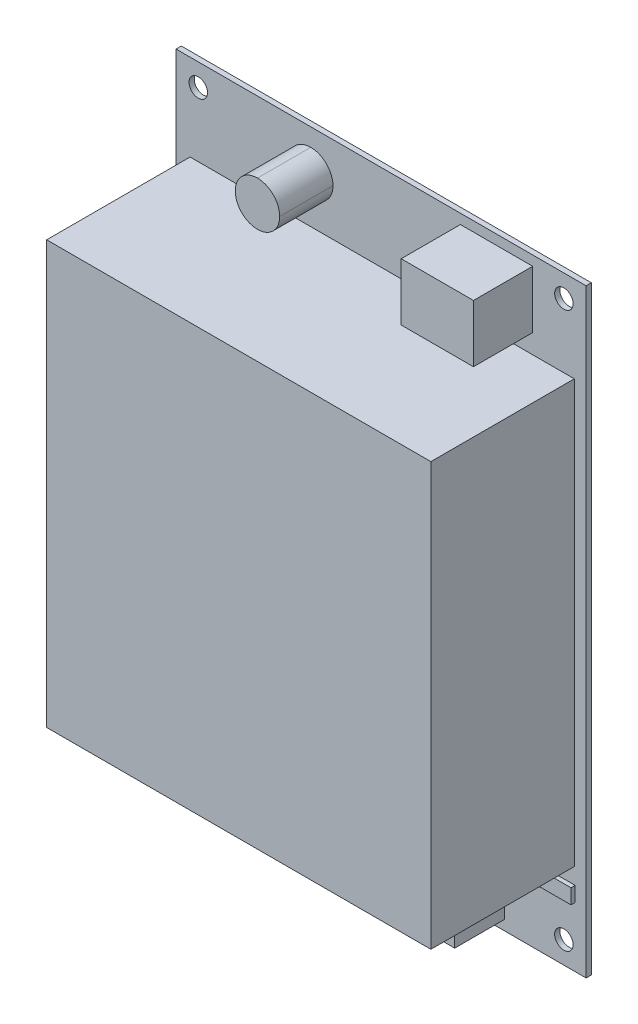
SolidWorks part; units mm, degrees
ref_plane "Front Plane" through (0, 0, 0) normal (0, 0, 1) x (1, 0, 0)
ref_plane "Top Plane" through (0, 0, 0) normal (0, 1, 0) x (1, 0, 0)
ref_plane "Right Plane" through (0, 0, 0) normal (1, 0, 0) x (0, 0, -1)
sketch "Sketch1" plane through (0, 0, 0) normal (0, 0, 1) x (1, 0, 0)
  line L0 (0, 102.87) -> (0, 0)
  line L1 (0, 0) -> (70.358, 0)
  line L2 (70.358, 0) -> (70.358, 102.87)
  line L3 (70.358, 102.87) -> (0, 102.87)
extrude "BOARD" add sketch "Sketch1" along normal blind 0.8992 separate body
ref_plane "Plane1" through (0, 0, 0.8992) normal (0, 0, 1) x (1, 0, 0)
sketch "Sketch48" plane through (0, 0, 0) normal (0, 0, 1) x (1, 0, 0)
  line L0 (20.447, 51.036) -> (22.987, 51.036)
  line L1 (22.987, 51.036) -> (22.987, 50.0659)
  line L2 (22.987, 50.0659) -> (20.447, 50.0659)
  line L3 (20.447, 50.0659) -> (20.447, 51.036)
extrude "0603-R-35" add sketch "Sketch48" against normal blind 0.508 separate body
sketch "Sketch49" plane through (0, 0, 0) normal (0, 0, 1) x (1, 0, 0)
  line L0 (20.447, 49.6331) -> (22.987, 49.6331)
  line L1 (22.987, 49.6331) -> (22.987, 48.6631)
  line L2 (22.987, 48.6631) -> (20.447, 48.6631)
  line L3 (20.447, 48.6631) -> (20.447, 49.6331)
extrude "0603-R-36" add sketch "Sketch49" against normal blind 0.508 separate body
sketch "Sketch50" plane through (0, 0, 0) normal (0, 0, 1) x (1, 0, 0)
  line L0 (20.447, 48.227) -> (22.987, 48.227)
  line L1 (22.987, 48.227) -> (22.987, 47.257)
  line L2 (22.987, 47.257) -> (20.447, 47.257)
  line L3 (20.447, 47.257) -> (20.447, 48.227)
extrude "0603-R-37" add sketch "Sketch50" against normal blind 0.508 separate body
sketch "Sketch59" plane through (0, 0, 0) normal (0, 0, 1) x (1, 0, 0)
  line L0 (22.987, 52.85) -> (20.447, 52.85)
  line L1 (20.447, 52.85) -> (20.447, 53.8201)
  line L2 (20.447, 53.8201) -> (22.987, 53.8201)
  line L3 (22.987, 53.8201) -> (22.987, 52.85)
extrude "0603-RB-1" add sketch "Sketch59" against normal blind 0.254 separate body
sketch "Sketch60" plane through (0, 0, 0) normal (0, 0, 1) x (1, 0, 0)
  line L0 (19.177, 50.056) -> (16.637, 50.056)
  line L1 (16.637, 50.056) -> (16.637, 51.0261)
  line L2 (16.637, 51.0261) -> (19.177, 51.0261)
  line L3 (19.177, 51.0261) -> (19.177, 50.056)
extrude "0603-R-44" add sketch "Sketch60" against normal blind 0.508 separate body
sketch "Sketch61" plane through (0, 0, 0) normal (0, 0, 1) x (1, 0, 0)
  line L0 (19.177, 47.262) -> (16.637, 47.262)
  line L1 (16.637, 47.262) -> (16.637, 48.2321)
  line L2 (16.637, 48.2321) -> (19.177, 48.2321)
  line L3 (19.177, 48.2321) -> (19.177, 47.262)
extrude "0603-RA-1" add sketch "Sketch61" against normal blind 0.254 separate body
sketch "Sketch62" plane through (0, 0, 0) normal (0, 0, 1) x (1, 0, 0)
  line L0 (16.637, 55.227) -> (19.177, 55.227)
  line L1 (19.177, 55.227) -> (19.177, 54.2569)
  line L2 (19.177, 54.2569) -> (16.637, 54.2569)
  line L3 (16.637, 54.2569) -> (16.637, 55.227)
extrude "0603-R-45" add sketch "Sketch62" against normal blind 0.508 separate body
sketch "Sketch63" plane through (0, 0, 0) normal (0, 0, 1) x (1, 0, 0)
  line L0 (16.637, 53.83) -> (19.177, 53.83)
  line L1 (19.177, 53.83) -> (19.177, 52.8599)
  line L2 (19.177, 52.8599) -> (16.637, 52.8599)
  line L3 (16.637, 52.8599) -> (16.637, 53.83)
extrude "0603-R-46" add sketch "Sketch63" against normal blind 0.508 separate body
sketch "Sketch64" plane through (0, 0, 0) normal (0, 0, 1) x (1, 0, 0)
  line L0 (19.177, 55.644) -> (16.637, 55.644)
  line L1 (16.637, 55.644) -> (16.637, 56.6141)
  line L2 (16.637, 56.6141) -> (19.177, 56.6141)
  line L3 (19.177, 56.6141) -> (19.177, 55.644)
extrude "0603-R-47" add sketch "Sketch64" against normal blind 0.508 separate body
sketch "Sketch65" plane through (0, 0, 0) normal (0, 0, 1) x (1, 0, 0)
  line L0 (19.177, 51.453) -> (16.637, 51.453)
  line L1 (16.637, 51.453) -> (16.637, 52.4231)
  line L2 (16.637, 52.4231) -> (19.177, 52.4231)
  line L3 (19.177, 52.4231) -> (19.177, 51.453)
extrude "0603-R-48" add sketch "Sketch65" against normal blind 0.508 separate body
sketch "Sketch66" plane through (0, 0, 0) normal (0, 0, 1) x (1, 0, 0)
  line L0 (23.0154, 51.466) -> (20.4754, 51.466)
  line L1 (20.4754, 51.466) -> (20.4754, 52.436)
  line L2 (20.4754, 52.436) -> (23.0154, 52.436)
  line L3 (23.0154, 52.436) -> (23.0154, 51.466)
extrude "0603-R-49" add sketch "Sketch66" against normal blind 0.508 separate body
sketch "Sketch67" plane through (0, 0, 0) normal (0, 0, 1) x (1, 0, 0)
  line L0 (16.637, 49.639) -> (19.177, 49.639)
  line L1 (19.177, 49.639) -> (19.177, 48.6689)
  line L2 (19.177, 48.6689) -> (16.637, 48.6689)
  line L3 (16.637, 48.6689) -> (16.637, 49.639)
extrude "0603-R-50" add sketch "Sketch67" against normal blind 0.508 separate body
sketch "Sketch74" plane through (0, 0, 0) normal (0, 0, 1) x (1, 0, 0)
  line L0 (22.987, 55.644) -> (20.447, 55.644)
  line L1 (20.447, 55.644) -> (20.447, 56.6141)
  line L2 (20.447, 56.6141) -> (22.987, 56.6141)
  line L3 (22.987, 56.6141) -> (22.987, 55.644)
extrude "0603-R-56" add sketch "Sketch74" against normal blind 0.508 separate body
sketch "Sketch75" plane through (0, 0, 0) normal (0, 0, 1) x (1, 0, 0)
  line L0 (22.987, 54.247) -> (20.447, 54.247)
  line L1 (20.447, 54.247) -> (20.447, 55.2171)
  line L2 (20.447, 55.2171) -> (22.987, 55.2171)
  line L3 (22.987, 55.2171) -> (22.987, 54.247)
extrude "0603-RB-2" add sketch "Sketch75" against normal blind 0.254 separate body
sketch "Sketch78" plane through (0, 0, 0.8992) normal (0, 0, 1) x (1, 0, 0)
  line L0 (16.637, 10.668) -> (9.017, 10.668)
  line L1 (9.017, 10.668) -> (9.017, 3.048)
  line L2 (9.017, 3.048) -> (16.637, 3.048)
  line L3 (16.637, 3.048) -> (16.637, 10.668)
extrude "SMA-50-TH-1" add sketch "Sketch78" along normal blind 9.144 separate body
sketch "Sketch79" plane through (0, 0, 0.8992) normal (0, 0, 1) x (1, 0, 0)
  line L0 (26.924, 99.822) -> (19.304, 99.822)
  line L1 (19.304, 99.822) -> (19.304, 92.202)
  line L2 (19.304, 92.202) -> (26.924, 92.202)
  line L3 (26.924, 92.202) -> (26.924, 99.822)
extrude "SMA-50-TH-2" add sketch "Sketch79" along normal blind 9.144 separate body
sketch "Sketch83" plane through (0, 0, 0.8992) normal (0, 0, 1) x (1, 0, 0)
  line L0 (54.356, 10.287) -> (60.104, 10.287)
  line L1 (60.104, 10.287) -> (60.104, 12.827)
  line L2 (60.104, 12.827) -> (54.356, 12.827)
  line L3 (54.356, 12.827) -> (54.356, 10.287)
extrude "0805_POL-1" add sketch "Sketch83" along normal blind 0.7112 separate body
sketch "Sketch84" plane through (0, 0, 0.8992) normal (0, 0, 1) x (1, 0, 0)
  line L0 (62.738, 10.287) -> (68.486, 10.287)
  line L1 (68.486, 10.287) -> (68.486, 12.827)
  line L2 (68.486, 12.827) -> (62.738, 12.827)
  line L3 (62.738, 12.827) -> (62.738, 10.287)
extrude "0805_POL-2" add sketch "Sketch84" along normal blind 0.7112 separate body
sketch "Sketch85" plane through (0, 0, 0.8992) normal (0, 0, 1) x (1, 0, 0)
  line L0 (61.359, 12.827) -> (61.359, 10.287)
  line L1 (61.359, 10.287) -> (62.3291, 10.287)
  line L2 (62.3291, 10.287) -> (62.3291, 12.827)
  line L3 (62.3291, 12.827) -> (61.359, 12.827)
extrude "0603-R-58" add sketch "Sketch85" along normal blind 0.508 separate body
sketch "Sketch86" plane through (0, 0, 0.8992) normal (0, 0, 1) x (1, 0, 0)
  line L0 (52.977, 12.827) -> (52.977, 10.287)
  line L1 (52.977, 10.287) -> (53.9471, 10.287)
  line L2 (53.9471, 10.287) -> (53.9471, 12.827)
  line L3 (53.9471, 12.827) -> (52.977, 12.827)
extrude "0603-R-59" add sketch "Sketch86" along normal blind 0.508 separate body
sketch "Sketch110" plane through (0, 0, 0.8992) normal (0, 0, 1) x (1, 0, 0)
  line L0 (25.654, 3.048) -> (33.274, 3.048)
  line L1 (33.274, 3.048) -> (33.274, 10.668)
  line L2 (33.274, 10.668) -> (25.654, 10.668)
  line L3 (25.654, 10.668) -> (25.654, 3.048)
extrude "SMA-50-TH-3" add sketch "Sketch110" along normal blind 9.144 separate body
sketch "Sketch117" plane through (0, 0, 0.8992) normal (0, 0, 1) x (1, 0, 0)
  line L0 (36.9931, 1.668) -> (47.4929, 1.668)
  line L1 (47.4929, 1.668) -> (47.4929, 7.8966)
  line L2 (47.4929, 7.8966) -> (36.9931, 7.8966)
  line L3 (36.9931, 7.8966) -> (36.9931, 1.668)
extrude "HDR_SHERLOCK_4P_V-1" add sketch "Sketch117" along normal blind 8.509 separate body
sketch "Sketch118" plane through (0, 0, 0.8992) normal (0, 0, 1) x (1, 0, 0)
  line L0 (61.1909, 101.1829) -> (48.7911, 101.1829)
  line L1 (48.7911, 101.1829) -> (48.7911, 91.329)
  line L2 (48.7911, 91.329) -> (61.1909, 91.329)
  line L3 (61.1909, 91.329) -> (61.1909, 101.1829)
extrude "HDR_MFITJR_2R2P-V-1" add sketch "Sketch118" along normal blind 10.16 separate body
sketch "Sketch119" plane through (0, 0, 0.8992) normal (0, 0, 1) x (1, 0, 0)
  line L0 (49.8201, 1.668) -> (56.3199, 1.668)
  line L1 (56.3199, 1.668) -> (56.3199, 7.972)
  line L2 (56.3199, 7.972) -> (49.8201, 7.972)
  line L3 (49.8201, 7.972) -> (49.8201, 1.668)
extrude "HDR_SHERLOCK_2P_V-1" add sketch "Sketch119" along normal blind 8.509 separate body
sketch "Sketch121" plane through (0, 0, 0) normal (0, 0, 1) x (1, 0, 0)
  line L0 (32.4599, 29.975) -> (38.814, 29.975)
  line L1 (38.814, 29.975) -> (38.814, 26.8209)
  line L2 (38.814, 26.8209) -> (32.4599, 26.8209)
  line L3 (32.4599, 26.8209) -> (32.4599, 29.975)
extrude "TSSOP8-1" add sketch "Sketch121" against normal blind 0.9906 separate body
sketch "Sketch122" plane through (0, 0, 0) normal (0, 0, 1) x (1, 0, 0)
  line L0 (37.1602, 21.6027) -> (37.1602, 26.5557)
  line L1 (37.1602, 26.5557) -> (38.9382, 26.5557)
  line L2 (38.9382, 26.5557) -> (38.9382, 21.6027)
  line L3 (38.9382, 21.6027) -> (37.1602, 21.6027)
extrude "1206-R-5" add sketch "Sketch122" against normal blind 0.508 separate body
sketch "Sketch124" plane through (0, 0, 0.8992) normal (0, 0, 1) x (1, 0, 0)
  line L0 (37.592, 10.287) -> (43.34, 10.287)
  line L1 (43.34, 10.287) -> (43.34, 12.827)
  line L2 (43.34, 12.827) -> (37.592, 12.827)
  line L3 (37.592, 12.827) -> (37.592, 10.287)
extrude "0805_POL-3" add sketch "Sketch124" along normal blind 0.7112 separate body
sketch "Sketch125" plane through (0, 0, 0.8992) normal (0, 0, 1) x (1, 0, 0)
  line L0 (45.974, 10.287) -> (51.722, 10.287)
  line L1 (51.722, 10.287) -> (51.722, 12.827)
  line L2 (51.722, 12.827) -> (45.974, 12.827)
  line L3 (45.974, 12.827) -> (45.974, 10.287)
extrude "0805_POL-4" add sketch "Sketch125" along normal blind 0.7112 separate body
sketch "Sketch126" plane through (0, 0, 0) normal (0, 0, 1) x (1, 0, 0)
  line L0 (35.6108, 25.3672) -> (33.0708, 25.3672)
  line L1 (33.0708, 25.3672) -> (33.0708, 26.3373)
  line L2 (33.0708, 26.3373) -> (35.6108, 26.3373)
  line L3 (35.6108, 26.3373) -> (35.6108, 25.3672)
extrude "0603-R-67" add sketch "Sketch126" against normal blind 0.508 separate body
sketch "Sketch127" plane through (0, 0, 0) normal (0, 0, 1) x (1, 0, 0)
  line L0 (39.878, 28.7348) -> (42.418, 28.7348)
  line L1 (42.418, 28.7348) -> (42.418, 27.7647)
  line L2 (42.418, 27.7647) -> (39.878, 27.7647)
  line L3 (39.878, 27.7647) -> (39.878, 28.7348)
extrude "0603-R-68" add sketch "Sketch127" against normal blind 0.508 separate body
sketch "Sketch128" plane through (0, 0, 0.8992) normal (0, 0, 1) x (1, 0, 0)
  line L0 (44.595, 12.827) -> (44.595, 10.287)
  line L1 (44.595, 10.287) -> (45.5651, 10.287)
  line L2 (45.5651, 10.287) -> (45.5651, 12.827)
  line L3 (45.5651, 12.827) -> (44.595, 12.827)
extrude "0603-R-69" add sketch "Sketch128" along normal blind 0.508 separate body
sketch "Sketch129" plane through (0, 0, 0.8992) normal (0, 0, 1) x (1, 0, 0)
  line L0 (37.193, 10.287) -> (37.193, 12.827)
  line L1 (37.193, 12.827) -> (36.2229, 12.827)
  line L2 (36.2229, 12.827) -> (36.2229, 10.287)
  line L3 (36.2229, 10.287) -> (37.193, 10.287)
extrude "0603-R-70" add sketch "Sketch129" along normal blind 0.508 separate body
sketch "Sketch130" plane through (0, 0, 0.8992) normal (0, 0, 1) x (1, 0, 0)
  line L0 (36.861, 84.2373) -> (36.861, 57.4373)
  line L1 (36.861, 57.4373) -> (46.197, 57.4373)
  line L2 (46.197, 57.4373) -> (46.197, 84.2373)
  line L3 (46.197, 84.2373) -> (36.861, 84.2373)
extrude "CAP_AXL_18MM_8MM-1" add sketch "Sketch130" along normal blind 12.4968 separate body
hole_wizard "1/8 (0.125) Diameter Hole1" positions "3DSketch1" profile "Sketch138" hole size "1/8" standard "Ansi Inch"
sketch3d "3DSketch1"
  point P0 (3.81, 99.06, 0.8992)
  point P2 (66.548, 99.06, 0.8992)
  point P4 (3.6372, 3.9715, 0.8992)
  point P6 (66.548, 3.81, 0.8992)
sketch "Sketch138" plane through (3.81, 99.06, 0.8992) normal (1, 0, 0) x (0, -1, 0)
  line L0 (0, 0) -> (0, 26.3539)
  line L1 (0, 26.3539) -> (1.5875, 25.4)
  line L2 (1.5875, 25.4) -> (1.5875, 0)
  line L5 (1.5875, 0) -> (0, 0)
  line L10 (0, 26.3539) -> (-1.5875, 25.4) construction
  line L11 (0, -6.35) -> (0, 107.95) construction
  dimension "Hole Dia." = 3.175
  dimension "Hole Depth" = 25.4
  dimension "Drill Angle" = 118
sketch "Sketch139" plane through (0, 0, 0.8992) normal (0, 0, 1) x (1, 0, 0)
  line L1 (2.4054, 88.0286) -> (68.3332, 88.0286)
  line L2 (2.4054, 88.0286) -> (2.4054, 15.5541)
  line L3 (2.4054, 15.5541) -> (68.3332, 15.5541)
  line L4 (68.3332, 88.0286) -> (68.3332, 15.5541)
extrude "Extrude126" add sketch "Sketch139" along normal blind 24.6091
fillet "Fillet3" radius 3.81 1 edges at (26.924, 92.202, 5.4712)
fillet "Fillet4" radius 3.81 1 edges at (26.924, 99.822, 5.4712)
fillet "Fillet5" radius 3.81 1 edges at (19.304, 99.822, 5.4712)
fillet "Fillet6" radius 3.81 1 edges at (19.304, 92.202, 5.4712)
fillet "Fillet7" radius 3.81 1 edges at (33.274, 10.668, 5.4712)
fillet "Fillet8" radius 3.81 1 edges at (33.274, 3.048, 5.4712)
fillet "Fillet9" radius 3.81 1 edges at (25.654, 3.048, 5.4712)
fillet "Fillet10" radius 3.81 1 edges at (25.654, 10.668, 5.4712)
fillet "Fillet11" radius 3.81 1 edges at (9.017, 3.048, 5.4712)
fillet "Fillet12" radius 3.81 1 edges at (9.017, 10.668, 5.4712)
fillet "Fillet13" radius 3.81 1 edges at (16.637, 3.048, 5.4712)
fillet "Fillet14" radius 3.81 1 edges at (16.637, 10.668, 5.4712)
